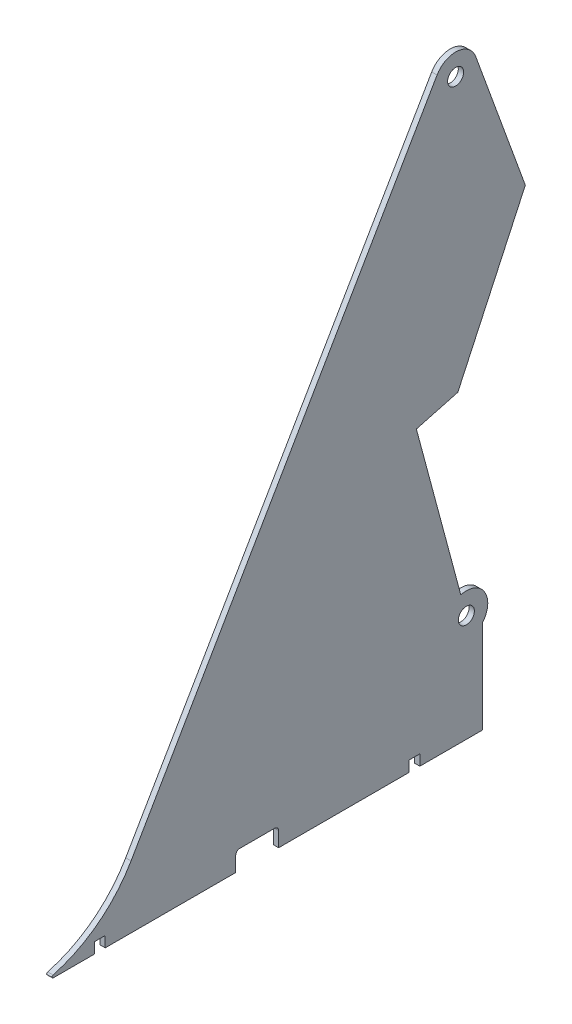
SolidWorks part; units mm, degrees
ref_plane "Front Plane" through (0, 0, 0) normal (0, 0, 1) x (1, 0, 0)
ref_plane "Top Plane" through (0, 0, 0) normal (0, 1, 0) x (1, 0, 0)
ref_plane "Right Plane" through (0, 0, 0) normal (1, 0, 0) x (0, 0, -1)
sketch "Sketch1" plane through (0, 0, 0) normal (1, 0, 0) x (0, 0, -1)
  line L0 (0, 0) -> (0, 55.0997)
  line L6 (-39.108, 173.9053) -> (-14.5735, 180.4793)
  line L7 (-14.5735, 180.4793) -> (25.4, 266.7)
  line L8 (25.4, 266.7) -> (-3.9421, 347.247)
  line L9 (-26.861, 349.2717) -> (-208.0116, 36.9339)
  line L10 (-254, 0) -> (0, 0)
  line L12 (-254.2054, 1.5605) -> (-207.9989, 13.9415) construction
  line L13 (-39.108, 173.9053) -> (-12.812, 75.7673)
  line L14 (-12.812, 75.7673) -> (13.738, 82.8813) construction
  arc A0 (-3.9421, 347.247) -> (-26.861, 349.2717) centre (-15.875, 342.9) ccw
  arc A1 (-254, 0) -> (-254.2054, 1.5605) centre (-254, 0.7937) cw
  arc A2 (-254.2054, 1.5605) -> (-208.0116, 36.9339) centre (-273.9274, 75.164) ccw
  arc A3 (0, 55.0997) -> (-12.812, 75.7673) centre (-9.525, 63.5) ccw
  point P14 (-15.875, 180.4158)
  point P15 (-208.0116, 13.9415)
  point P16 (25.9788, 268.7978)
  point P18 (-12.5805, 180.5536)
  point P19 (-36.3283, 174.6129)
  dimension "D2" = 12.7
  dimension "D6" = 0.7937
  dimension "D7" = 76.2
  dimension "D12" = 12.7
  dimension "D1" = 15.875
  dimension "D3" = 342.9
  dimension "D4" = 25.4
  dimension "D5" = 101.6
  dimension "D8" = 254
  dimension "D9" = 15
  dimension "D10" = 9.525
  dimension "D11" = 63.5
  dimension "D13" = 76.2
  dimension "D14" = 25.4
  dimension "D15" = 15
extrude "Boss-Extrude1" add sketch "Sketch1" along normal blind 3.175
sketch "Sketch2" plane through (3.175, 0, 0) normal (1, 0, 0) x (0, 0, -1)
  line L0 (-37.0504, 6.35) -> (-43.4004, 6.35) construction
  line L1 (-37.0504, 0) -> (-37.0504, 6.35) construction
  line L2 (-43.4004, 0) -> (-37.0504, 0) construction
  line L3 (-43.4004, 6.35) -> (-43.4004, 0) construction
  line L4 (-37.0504, 6.35) -> (-43.4004, 6.35)
  line L5 (-37.0504, 0) -> (-37.0504, 6.35)
  line L6 (-43.4004, 0) -> (-37.0504, 0)
  line L7 (-43.4004, 6.35) -> (-43.4004, 0)
  line L8 (-223.2996, 6.35) -> (-229.6496, 6.35) construction
  line L9 (-223.2996, 0) -> (-223.2996, 6.35) construction
  line L10 (-229.6496, 0) -> (-223.2996, 0) construction
  line L11 (-229.6496, 6.35) -> (-229.6496, 0) construction
  line L12 (-223.2996, 6.35) -> (-229.6496, 6.35)
  line L13 (-223.2996, 0) -> (-223.2996, 6.35)
  line L14 (-229.6496, 0) -> (-223.2996, 0)
  line L15 (-229.6496, 6.35) -> (-229.6496, 0)
  line L16 (-146.05, 8.7909) -> (-146.05, -0.3034) construction
  line L17 (-123.0376, 11.1785) -> (-143.6624, 11.1785) construction
  line L18 (-120.65, -0.3034) -> (-120.65, 8.7909) construction
  line L19 (-146.05, 8.7909) -> (-146.05, 0)
  line L20 (-123.0376, 11.1785) -> (-143.6624, 11.1785)
  line L21 (-120.65, 0) -> (-120.65, 8.7909)
  line L25 (-146.05, 0) -> (-120.65, 0)
  line L26 (-254, 0) -> (0, 0) construction
  arc A0 (-143.6624, 11.1785) -> (-146.05, 8.7909) centre (-143.6624, 8.7909) ccw construction
  arc A1 (-120.65, 8.7909) -> (-123.0376, 11.1785) centre (-123.0376, 8.7909) ccw construction
  arc A2 (-143.6624, 11.1785) -> (-146.05, 8.7909) centre (-143.6624, 8.7909) ccw
  arc A3 (-120.65, 8.7909) -> (-123.0376, 11.1785) centre (-123.0376, 8.7909) ccw
extrude "Cut-Extrude1" cut sketch "Sketch2" against normal through all
sketch "Sketch3" plane through (3.175, 0, 0) normal (1, 0, 0) x (0, 0, -1)
  point P0 (-15.875, 342.9)
  point P4 (-9.525, 63.5)
hole_wizard "3/8 Clearance Hole1" positions "Sketch3" profile "Sketch4" hole size "3/8" standard "ANSI Inch" end condition up to next
sketch "Sketch4" plane through (3.175, 342.9, 15.875) normal (0, 1, 0) x (0, 0, -1)
  line L0 (0, 0) -> (0, 3.175)
  line L1 (0, 3.175) -> (4.7625, 3.175)
  line L2 (4.7625, 3.175) -> (4.7625, 0)
  line L5 (4.7625, 0) -> (0, 0)
  line L11 (0, -6.35) -> (0, 107.95) construction
  dimension "Thru Hole Dia." = 9.525
  dimension "Thru Hole Depth" = 3.175
sketch "Sketch5" plane through (3.175, 0, 0) normal (1, 0, 0) x (0, 0, -1)
  line L0 (-9.525, 63.5) -> (25.2029, 26.4242)
  line L1 (25.2029, 26.4242) -> (24.793, 13.8877)
  line L2 (20.8619, 31.0587) -> (-25.3801, 19.6651)
  line L3 (-15.875, 19.05) -> (-25.3801, 19.6651)
  line L4 (0, 0) -> (0, 55.0997) construction
  line L5 (-15.875, 19.05) -> (-30.1872, 6.4776)
  line L6 (-30.1872, 6.4776) -> (-54.7505, 169.5016)
  line L7 (50.8, 0) -> (50.8, 73.5762) construction
  point P7 (-27.3447, 34.2601)
  point P11 (-32.5707, 28.1962)
  point P12 (-54.7505, 169.5016)
  point P14 (-24.2336, 36.1683)
  point P15 (-22.3554, 36.9639)
  point P17 (-30.4441, 31.3237)
  point P18 (-29.186, 5.4221)
  point P19 (-30.1872, 6.4776)
  dimension "D1" = 44.45
  dimension "D2" = 50.8
  dimension "D3" = 45
  dimension "D4" = 60.325
  dimension "D5" = 19.05
  dimension "D6" = 15.875
  dimension "D7" = 9.525
  dimension "D8" = 47.625
  dimension "D9" = 19.05
  dimension "D10" = 45
  dimension "D11" = 50.8
